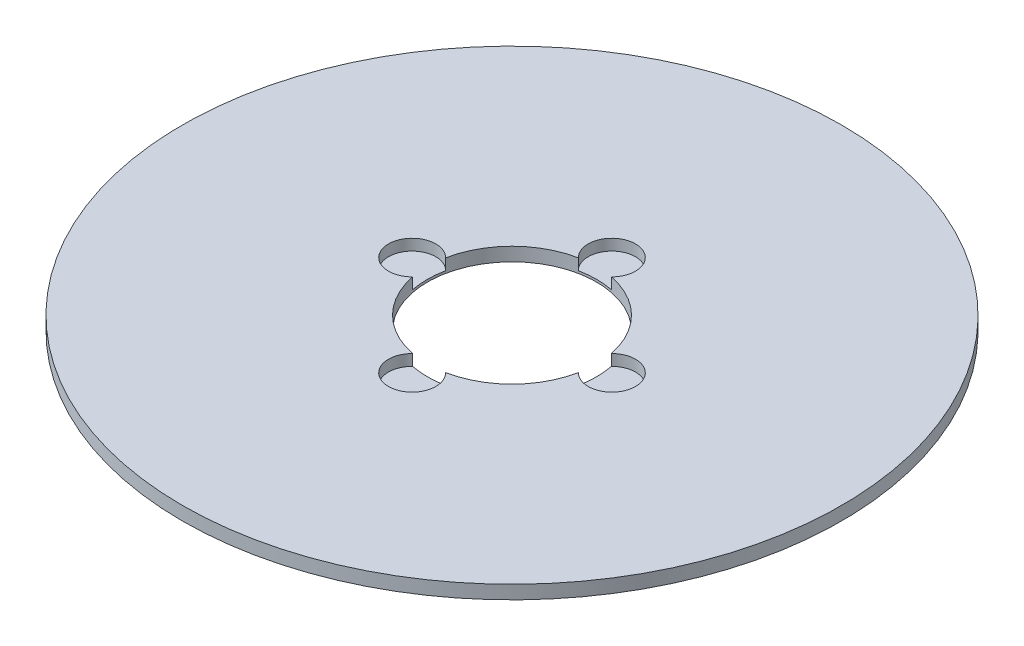
SolidWorks part; units mm, degrees
ref_plane "Front Plane" through (0, 0, 0) normal (0, 0, 1) x (1, 0, 0)
ref_plane "Top Plane" through (0, 0, 0) normal (0, 1, 0) x (1, 0, 0)
ref_plane "Right Plane" through (0, 0, 0) normal (1, 0, 0) x (0, 0, -1)
sketch "Sketch1" plane through (0, 0, 0) normal (0, 1, 0) x (1, 0, 0)
  circle A0 centre (0, 0) radius 97.5
  dimension "FLANGE_OD" = 195
extrude "Boss-Extrude1" add sketch "Sketch1" along normal blind 4
sketch "Sketch2" plane through (0, 0, 0) normal (0, 1, 0) x (1, 0, 0)
  circle A0 centre (0, 0) radius 25
  dimension "BORE_D" = 50
extrude "Cut-Extrude1" cut sketch "Sketch2" along normal through all
sketch "Sketch3" plane through (0, 4, 0) normal (0, 1, 0) x (1, 0, 0)
  circle A0 centre (0, 0) radius 29.5405 construction
  circle A1 centre (-29.5405, 0) radius 7.0001
  dimension "BOLT_D" = 14.0002
  dimension "BOLT_PCD" = 59.0809
extrude "Cut-Extrude2" cut sketch "Sketch3" against normal blind 3.2921
pattern_circular "CirPattern1" count 4 over 360 about axis through (0, 0, 0) along (0, 1, 0) of "Cut-Extrude2"
